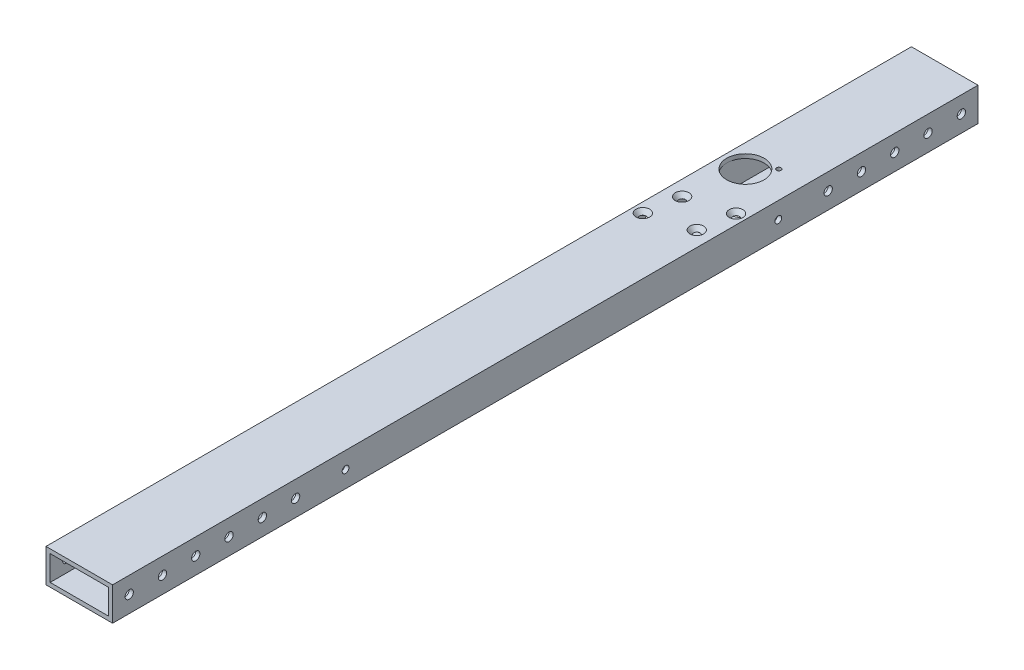
SolidWorks part; units mm, degrees
material "6061 Alloy"
ref_plane "Front Plane" through (0, 0, 0) normal (0, 0, 1) x (1, 0, 0)
ref_plane "Top Plane" through (0, 0, 0) normal (0, 1, 0) x (1, 0, 0)
ref_plane "Right Plane" through (0, 0, 0) normal (1, 0, 0) x (0, 0, -1)
sketch "Sketch1" plane through (0, 0, 0) normal (0, 0, 1) x (1, 0, 0)
  line L0 (-22.225, 9.525) -> (22.225, 9.525)
  line L2 (-25.4, 12.7) -> (25.4, 12.7)
  line L3 (-25.4, 12.7) -> (-25.4, -12.7)
  line L4 (-25.4, -12.7) -> (25.4, -12.7)
  line L5 (25.4, 12.7) -> (25.4, -12.7)
  line L10 (22.225, 9.525) -> (22.225, -9.525)
  line L11 (-22.225, -9.525) -> (22.225, -9.525)
  line L12 (-22.225, 9.525) -> (-22.225, -9.525)
  point P12 (0, 12.7)
  point P14 (25.4, 0)
  dimension "Wall Thickness" = 3.175
  dimension "Outside Width" = 50.8
  dimension "Outside Height" = 25.4
  dimension "Inside Height" = 19.05
  dimension "Inside Width" = 44.45
sketch "Sketch2" plane through (0, 0, 0) normal (1, 0, 0) x (0, 0, -1)
  line L0 (330.2, 0) -> (-330.2, 0)
  point P4 (0, 0)
  point P7 (-330.2, 0)
  point P10 (330.2, 0)
  dimension "Length" = 660.4
sketch "Sketch3" plane through (0, 0, 0) normal (0, 0, 1) x (1, 0, 0)
  line L21 (25.4, 12.7) -> (-25.4, 12.7)
  line L22 (25.4, -12.7) -> (25.4, 12.7)
  line L23 (-25.4, -12.7) -> (25.4, -12.7)
  line L24 (-25.4, 12.7) -> (-25.4, -12.7)
  line L25 (25.4, 12.7) -> (-25.4, 12.7)
  line L26 (25.4, -12.7) -> (25.4, 12.7)
  line L27 (-25.4, -12.7) -> (25.4, -12.7)
  line L28 (-25.4, 12.7) -> (-25.4, -12.7)
  line L29 (22.225, 9.525) -> (-22.225, 9.525)
  line L30 (22.225, -9.525) -> (22.225, 9.525)
  line L31 (-22.225, -9.525) -> (22.225, -9.525)
  line L32 (-22.225, 9.525) -> (-22.225, -9.525)
  line L33 (22.225, 9.525) -> (-22.225, 9.525)
  line L34 (22.225, -9.525) -> (22.225, 9.525)
  line L35 (-22.225, -9.525) -> (22.225, -9.525)
  line L36 (-22.225, 9.525) -> (-22.225, -9.525)
  dimension "D1" = 0
  dimension "D2" = 0
extrude "Boss-Extrude1" add sketch "Sketch3" along normal up to vertex (330.2 mm away) and the other way up to vertex (330.2 mm away) up to point (0, 0, 330.2) other way up to point (0, 0, -330.2)
sketch "Drawing Reference" plane through (0, 0, 0) normal (1, 0, 0) x (0, 0, -1)
  line L0 (-330.2, 0) -> (330.2, 0) construction
  line L1 (0, -12.7) -> (0, 12.7) construction
  line L2 (-330.2, -12.7) -> (330.2, -12.7) construction
  line L5 (-330.2, 12.7) -> (330.2, 12.7) construction
  point P7 (-293.624, 0)
  point P8 (293.624, 0)
  dimension "D1" = 36.576
sketch "Sketch5" plane through (25.4, 0, 0) normal (1, 0, 0) x (0, 0, -1)
  line L2 (-266.7, 0) -> (-241.3, 0)
  line L3 (-241.3, 0) -> (-215.9, 0)
  line L4 (-215.9, 0) -> (-190.5, 0)
  line L5 (-317.5, 0) -> (-330.2, 0)
  line L6 (-330.2, -12.7) -> (-330.2, 12.7) construction
  line L7 (-317.5, 0) -> (-292.1, 0)
  line L8 (-292.1, 0) -> (-266.7, 0)
sketch "Sketch8" plane through (25.4, 0, 0) normal (1, 0, 0) x (0, 0, -1)
  line L0 (330.2, 0) -> (292.1, 0)
  line L1 (330.2, -12.7) -> (330.2, 12.7) construction
  line L2 (292.1, 0) -> (266.7, 0)
  line L3 (266.7, 0) -> (241.3, 0)
  line L4 (241.3, 0) -> (215.9, 0)
  line L5 (330.2, 0) -> (317.5, 0)
hole_wizard "1/4 (0.25) Diameter Hole3" positions "Sketch12" profile "Sketch13" hole size "1/4" standard "ANSI Inch" end condition through all
sketch "Sketch12" plane through (-25.4, 0, 0) normal (-1, 0, 0) x (0, 0, 1)
  point P4 (-317.5, 0)
sketch "Sketch13" plane through (-25.4, 0, -317.5) normal (0, 1, 0) x (0, 0, 1)
  line L0 (0, 0) -> (0, 50.8)
  line L1 (0, 50.8) -> (3.175, 50.8)
  line L2 (3.175, 50.8) -> (3.175, 0)
  line L5 (3.175, 0) -> (0, 0)
  line L11 (0, -6.35) -> (0, 107.95) construction
  dimension "Thru Hole Dia." = 6.35
  dimension "Thru Hole Depth" = 50.8
hole_wizard "1/4 (0.25) Diameter Hole4" positions "Sketch14" profile "Sketch15" hole size "1/4" standard "ANSI Inch" end condition through all
sketch "Sketch14" plane through (-25.4, 0, 0) normal (-1, 0, 0) x (0, 0, 1)
  point P0 (292.1, 0)
  point P3 (317.5, 0)
sketch "Sketch15" plane through (-25.4, 0, 292.1) normal (0, 1, 0) x (0, 0, 1)
  line L0 (0, 0) -> (0, 50.8)
  line L1 (0, 50.8) -> (3.175, 50.8)
  line L2 (3.175, 50.8) -> (3.175, 0)
  line L5 (3.175, 0) -> (0, 0)
  line L11 (0, -6.35) -> (0, 107.95) construction
  dimension "Thru Hole Dia." = 6.35
  dimension "Thru Hole Depth" = 50.8
hole_wizard "1/4 (0.25) Diameter Hole5" positions "Sketch17" profile "Sketch18" hole size "1/4" standard "ANSI Inch" end condition through all
sketch "Sketch17" plane through (25.4, 0, 0) normal (1, 0, 0) x (0, 0, -1)
  point P0 (292.1, 0)
  point P3 (266.7, 0)
sketch "Sketch18" plane through (25.4, 0, -292.1) normal (0, 1, 0) x (0, 0, -1)
  line L0 (0, 0) -> (0, 50.8)
  line L1 (0, 50.8) -> (3.175, 50.8)
  line L2 (3.175, 50.8) -> (3.175, 0)
  line L5 (3.175, 0) -> (0, 0)
  line L11 (0, -6.35) -> (0, 107.95) construction
  dimension "Thru Hole Dia." = 6.35
  dimension "Thru Hole Depth" = 50.8
hole_wizard "1/4 (0.25) Diameter Hole6" positions "Sketch19" profile "Sketch20" hole size "1/4" standard "ANSI Inch" end condition through all
sketch "Sketch19" plane through (25.4, 0, 0) normal (1, 0, 0) x (0, 0, -1)
  point P0 (215.9, 0)
  point P3 (241.3, 0)
sketch "Sketch20" plane through (25.4, 0, -215.9) normal (0, 1, 0) x (0, 0, -1)
  line L0 (0, 0) -> (0, 50.8)
  line L1 (0, 50.8) -> (3.175, 50.8)
  line L2 (3.175, 50.8) -> (3.175, 0)
  line L5 (3.175, 0) -> (0, 0)
  line L11 (0, -6.35) -> (0, 107.95) construction
  dimension "Thru Hole Dia." = 6.35
  dimension "Thru Hole Depth" = 50.8
hole_wizard "1/4 (0.25) Diameter Hole7" positions "Sketch21" profile "Sketch22" hole size "1/4" standard "ANSI Inch" end condition through all
sketch "Sketch21" plane through (25.4, 0, 0) normal (1, 0, 0) x (0, 0, -1)
  point P0 (-190.5, 0)
  point P3 (-215.9, 0)
sketch "Sketch22" plane through (25.4, 0, 190.5) normal (0, 1, 0) x (0, 0, -1)
  line L0 (0, 0) -> (0, 50.8)
  line L1 (0, 50.8) -> (3.175, 50.8)
  line L2 (3.175, 50.8) -> (3.175, 0)
  line L5 (3.175, 0) -> (0, 0)
  line L11 (0, -6.35) -> (0, 107.95) construction
  dimension "Thru Hole Dia." = 6.35
  dimension "Thru Hole Depth" = 50.8
hole_wizard "1/4 (0.25) Diameter Hole8" positions "Sketch23" profile "Sketch24" hole size "1/4" standard "ANSI Inch" end condition through all
sketch "Sketch23" plane through (25.4, 0, 0) normal (1, 0, 0) x (0, 0, -1)
  point P0 (-266.7, 0)
  point P3 (-241.3, 0)
sketch "Sketch24" plane through (25.4, 0, 266.7) normal (0, 1, 0) x (0, 0, -1)
  line L0 (0, 0) -> (0, 50.8)
  line L1 (0, 50.8) -> (3.175, 50.8)
  line L2 (3.175, 50.8) -> (3.175, 0)
  line L5 (3.175, 0) -> (0, 0)
  line L11 (0, -6.35) -> (0, 107.95) construction
  dimension "Thru Hole Dia." = 6.35
  dimension "Thru Hole Depth" = 50.8
sketch "Sketch25" plane through (25.4, 0, 0) normal (1, 0, 0) x (0, 0, -1)
  line L0 (-190.5, 0) -> (-152.4, 0)
  line L1 (215.9, 0) -> (177.8, 0)
hole_wizard "13/64 (0.20313) Diameter Hole1" positions "Sketch26" profile "Sketch27" hole size "13/64" standard "ANSI Inch" end condition through all
sketch "Sketch26" plane through (25.4, 0, 0) normal (1, 0, 0) x (0, 0, -1)
  point P0 (-152.4, 0)
  point P3 (177.8, 0)
sketch "Sketch27" plane through (25.4, 0, 152.4) normal (0, 1, 0) x (0, 0, -1)
  line L0 (0, 0) -> (0, 50.8)
  line L1 (0, 50.8) -> (2.5798, 50.8)
  line L2 (2.5798, 50.8) -> (2.5798, 0)
  line L5 (2.5798, 0) -> (0, 0)
  line L11 (0, -6.35) -> (0, 107.95) construction
  dimension "Thru Hole Dia." = 5.1595
  dimension "Thru Hole Depth" = 50.8
sketch "Sketch28" plane through (-25.4, 0, 0) normal (-1, 0, 0) x (0, 0, 1)
  line L0 (103.1875, 0) -> (77.7875, 0)
  line L1 (-103.1875, 0) -> (-128.5875, 0)
hole_wizard "1/2 (0.5) Diameter Hole1" positions "Sketch29" profile "Sketch30" hole size "1/2" standard "ANSI Inch"
sketch "Sketch29" plane through (-25.4, 0, 0) normal (-1, 0, 0) x (0, 0, 1)
  point P1 (-591.3016, -480.8022)
  point P3 (-103.1875, 0)
  point P6 (77.7875, 0)
  point P9 (103.1875, 0)
  point P13 (-128.5875, 0)
sketch "Sketch30" plane through (-25.4, -480.8022, -591.3016) normal (0, 1, 0) x (0, 0, 1)
  line L0 (0, 0) -> (0, 10.1655)
  line L1 (0, 10.1655) -> (6.35, 6.35)
  line L2 (6.35, 6.35) -> (6.35, 0)
  line L5 (6.35, 0) -> (0, 0)
  line L10 (0, 10.1655) -> (-6.35, 6.35) construction
  line L11 (0, -6.35) -> (0, 107.95) construction
  dimension "Hole Dia." = 12.7
  dimension "Hole Depth" = 6.35
  dimension "Drill Angle" = 118
sketch "Sketch35" plane through (0, -12.7, 0) normal (0, -1, 0) x (1, 0, 0)
  line L0 (25.4, -169.4217) -> (-25.4, -154.3741) construction
  line L1 (-25.4, -154.3741) -> (575.1111, -332.2536) construction
  line L2 (25.4, 330.2) -> (25.4, -330.2) construction
  line L3 (-25.4, -154.3741) -> (-25.4, -205.571) construction
  line L4 (-7.9375, -186.0376) -> (4.8145, -198.7896) construction
  line L5 (-25.4, 330.2) -> (-25.4, -330.2) construction
  line L6 (-22.225, -154.3741) -> (-22.225, -205.571) construction
  line L10 (22.3239, -180.1003) -> (-28.5561, -165.029) construction
  line L11 (22.2439, -180.0766) -> (-28.5561, -165.029) construction
  circle A1 centre (-7.9375, -186.0376) radius 14.2875
  dimension "D1" = 3.175
  dimension "D2" = 11.1125
sketch "Sketch32" plane through (0, -12.7, 0) normal (0, -1, 0) x (1, 0, 0)
  line L1 (17.931, -153.0367) -> (13.819, -127.1821) construction
  line L2 (-13.819, -143.6319) -> (17.931, -153.0367) construction
  line L3 (-17.931, -117.7773) -> (13.819, -127.1821) construction
  line L4 (-13.819, -143.6319) -> (-17.931, -117.7773) construction
hole_wizard "#10 Clearance Hole1" positions "Sketch33" profile "Sketch34" hole size "#10" standard "ANSI Inch" end condition through all
sketch "Sketch33" plane through (0, -12.7, 0) normal (0, -1, 0) x (-1, 0, 0)
  point P0 (13.819, 143.6319)
  point P3 (17.931, 117.7773)
  point P6 (-13.819, 127.1821)
  point P9 (-17.931, 153.0367)
sketch "Sketch34" plane through (-13.819, -12.7, -143.6319) normal (1, 0, 0) x (0, 0, -1)
  line L0 (0, 0) -> (0, 25.4)
  line L1 (0, 25.4) -> (5.2197, 25.4)
  line L2 (2.4892, 22.2589) -> (2.4892, 0)
  line L5 (2.4892, 0) -> (0, 0)
  line L7 (5.2197, 25.4) -> (2.4892, 22.2589)
  line L8 (-5.2197, 25.4) -> (-2.4892, 22.2589) construction
  line L11 (0, -6.35) -> (0, 107.95) construction
  dimension "Thru Hole Dia." = 4.9784
  dimension "Thru Hole Depth" = 25.4
  dimension "Far C'Sink Dia." = 10.4394
  dimension "Far C'Sink Angle" = 82
extrude "Cut-Extrude1" cut sketch "Sketch35" against normal through all
hole_wizard "Tap Drill for #8-32 Tap1" positions "Sketch36" profile "Sketch37" hole size "#8-32" standard "ANSI Inch" end condition through all
sketch "Sketch36" plane through (0, -12.7, 0) normal (0, -1, 0) x (-1, 0, 0)
  point P0 (-4.8145, 198.7896)
sketch "Sketch37" plane through (4.8145, -12.7, -198.7896) normal (1, 0, 0) x (0, 0, -1)
  line L0 (0, 0) -> (0, 25.4)
  line L1 (0, 25.4) -> (1.7272, 25.4)
  line L2 (1.7272, 25.4) -> (1.7272, 0)
  line L5 (1.7272, 0) -> (0, 0)
  line L11 (0, -6.35) -> (0, 107.95) construction
  dimension "Thru Hole Dia." = 3.4544
  dimension "Thru Hole Depth" = 25.4
equation "\"D1@Drawing Reference\"=\"Outside Width@Sketch1\" * 0.72"
